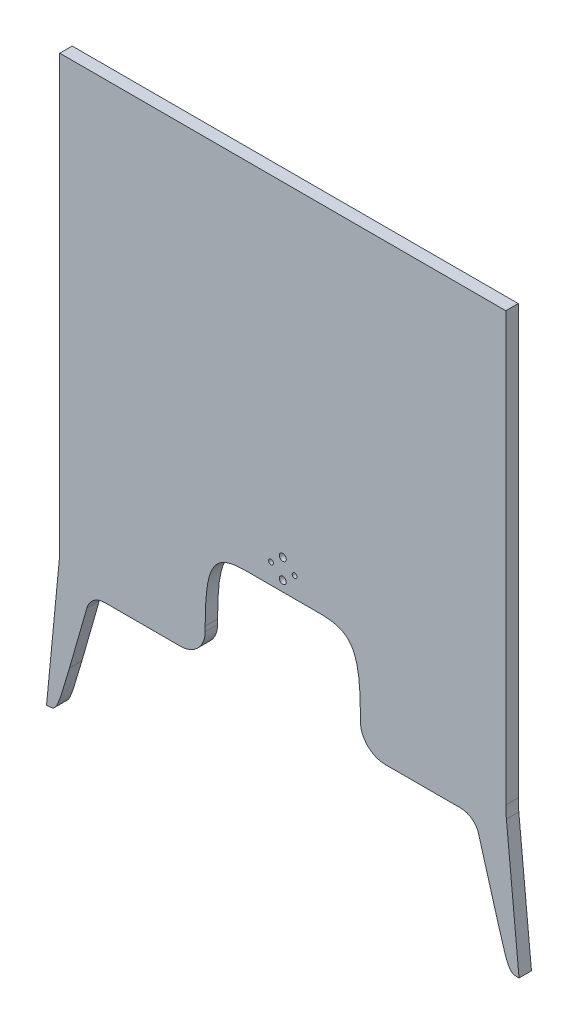
SolidWorks part; units mm, degrees
material "MDF"
ref_plane "Front Plane" through (0, 0, 0) normal (0, 0, 1) x (1, 0, 0)
ref_plane "Top Plane" through (0, 0, 0) normal (0, 1, 0) x (1, 0, 0)
ref_plane "Right Plane" through (0, 0, 0) normal (1, 0, 0) x (0, 0, -1)
sketch "Sketch1" plane through (0, 0, 0) normal (0, 0, 1) x (1, 0, 0)
  line L0 (-228.0888, 0) -> (228.0888, 0)
  line L1 (79.375, -363.22) -> (-79.375, -363.22)
  line L2 (0, -363.22) -> (0, 0) construction
  line L3 (-79.375, -363.22) -> (-79.375, -463.55)
  line L4 (196.3388, -463.55) -> (79.375, -463.55)
  line L5 (-230.9346, -584.2) -> (-196.3388, -463.55)
  line L6 (-230.9346, -584.2) -> (-241.6001, -584.2)
  line L7 (-241.6001, -584.2) -> (-228.0888, -443.879)
  line L8 (-228.0888, -443.879) -> (-228.0888, 0)
  line L9 (-196.3388, -463.55) -> (-79.375, -463.55)
  line L10 (228.0888, -443.879) -> (228.0888, 0)
  line L11 (241.6001, -584.2) -> (228.0888, -443.879)
  line L12 (230.9346, -584.2) -> (241.6001, -584.2)
  line L13 (230.9346, -584.2) -> (196.3388, -463.55)
  line L14 (79.375, -363.22) -> (79.375, -463.55)
  dimension "D1" = 363.22
  dimension "D2" = 158.75
  dimension "D3" = 106
  dimension "D4" = 31.75
  dimension "D5" = 120.65
  dimension "D6" = 174.5
  dimension "D7" = 463.55
  dimension "D8" = 140.97
extrude "Boss-Extrude1" add sketch "Sketch1" along normal blind 12.7
fillet "Fillet2" radius 69.85 1 edges at (-79.375, -363.22, 6.35) second distance 41.275 conic rho 0.6 first distance on face at (-79.375, -413.385, 6.35)
fillet "Fillet3" radius 25.4 1 edges at (-79.375, -463.55, 6.35)
fillet "Fillet4" radius 19.05 1 edges at (-196.3388, -463.55, 6.35)
ref_plane "Plane1" through (-230.9346, -584.2, 0) normal (0, 0, -1) x (-1, 0, 0)
fillet "Fillet5" radius 22.225 1 edges at (-230.9346, -584.2, 6.35) second distance 50.8 conic rho 0.7 first distance on face at (-236.2674, -584.2, 6.35)
fillet "Fillet6" radius 127 1 edges at (-228.0888, -443.879, 6.35)
sketch "Sketch3" plane through (0, 0, 12.7) normal (0, 0, 1) x (1, 0, 0)
  line L0 (0, 0) -> (0, -440.5951) construction
  line L2 (228.0888, 0) -> (-228.0888, 0) construction
  line L4 (0, 0) -> (241.6001, 0)
  line L5 (0, 0) -> (0, -584.2)
  line L6 (0, -584.2) -> (241.6001, -584.2)
  line L7 (241.6001, 0) -> (241.6001, -584.2)
  point P3 (0, 0)
extrude "Cut-Extrude1" cut sketch "Sketch3" against normal up to next
mirror "Mirror5" about plane through (0, 0, -0.3502) normal (-1, 0, 0) of bodies 103
hole_wizard "#8 Clearance Hole1" positions "Sketch4" profile "Sketch5" hole size "#8" standard "ANSI Inch" end condition up to next
sketch "Sketch4" plane through (0, 0, 0) normal (0, 0, -1) x (-1, 0, 0)
  circle A0 centre (12.0772, -342.5825) radius 2.4574 construction
  circle A1 centre (-12.0772, -342.5825) radius 2.4574 construction
  point P0 (12.0772, -342.5825)
  point P2 (-12.0772, -342.5825)
  point P5 (0, 0)
  point P8 (0, 0)
sketch "Sketch5" plane through (-12.0772, -342.5825, 0) normal (1, 0, 0) x (0, 1, 0)
  line L0 (0, 0) -> (0, 12.7)
  line L1 (0, 12.7) -> (2.4574, 12.7)
  line L2 (2.4574, 12.7) -> (2.4574, 0)
  line L5 (2.4574, 0) -> (0, 0)
  line L11 (0, -6.35) -> (0, 107.95) construction
  dimension "Thru Hole Dia." = 4.9149
  dimension "Thru Hole Depth" = 12.7
hole_wizard "1/4 Clearance Hole1" positions "Sketch6" profile "Sketch7" hole size "1/4" standard "ANSI Inch" end condition up to next
sketch "Sketch6" plane through (0, 0, 0) normal (0, 0, -1) x (-1, 0, 0)
  circle A0 centre (0, -352.7425) radius 3.5712 construction
  circle A1 centre (0, -332.4225) radius 3.5712 construction
  point P0 (0, -352.7425)
  point P2 (0, -332.4225)
  point P5 (0, 0)
  point P8 (0, 0)
sketch "Sketch7" plane through (0, -352.7425, 0) normal (1, 0, 0) x (0, 1, 0)
  line L0 (0, 0) -> (0, 12.7)
  line L1 (0, 12.7) -> (3.5712, 12.7)
  line L2 (3.5712, 12.7) -> (3.5712, 0)
  line L5 (3.5712, 0) -> (0, 0)
  line L11 (0, -6.35) -> (0, 107.95) construction
  dimension "Thru Hole Dia." = 7.1425
  dimension "Thru Hole Depth" = 12.7
